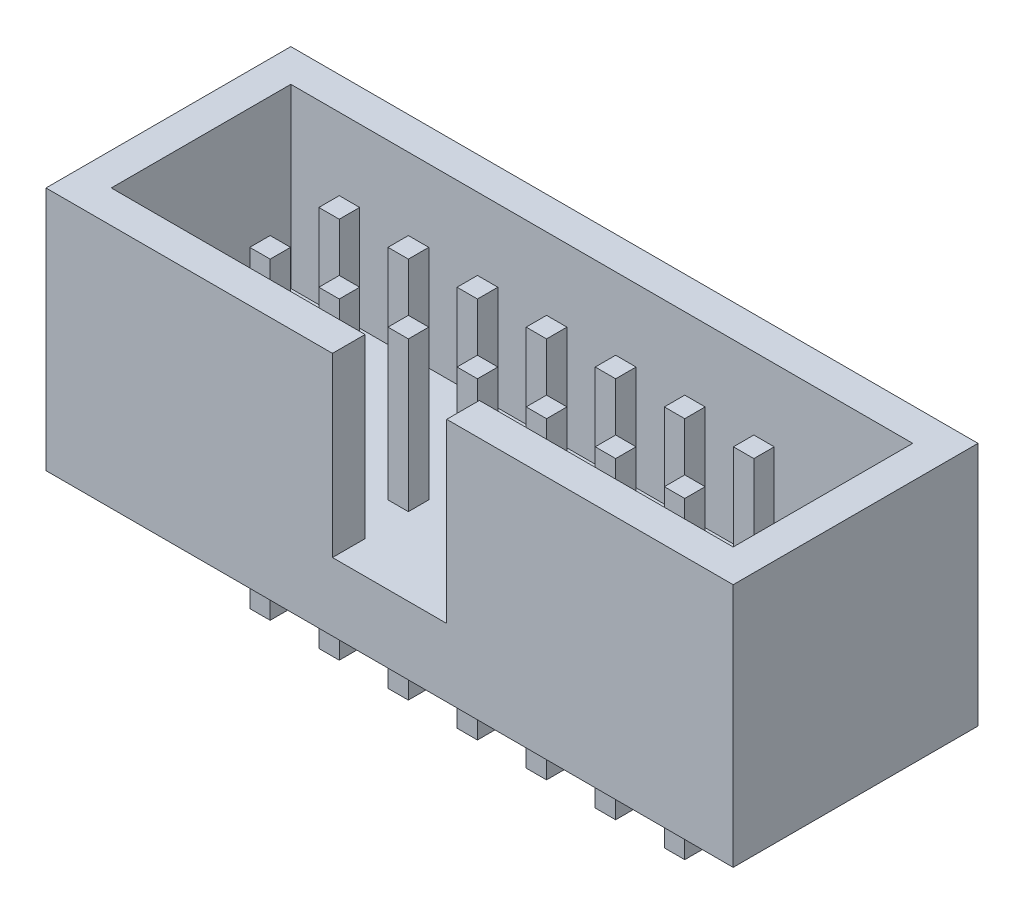
SolidWorks part; units mm, degrees
ref_plane "前视基准面" through (0, 0, 0) normal (0, 0, 1) x (1, 0, 0)
ref_plane "上视基准面" through (0, 0, 0) normal (0, 1, 0) x (1, 0, 0)
ref_plane "右视基准面" through (0, 0, 0) normal (1, 0, 0) x (0, 0, -1)
sketch "草图1" plane through (0, 0, 0) normal (0, 1, 0) x (1, 0, 0)
  line L0 (0, 85.0964) -> (0, -118.2031) construction
  line L1 (-12.63, 4.5) -> (12.63, 4.5)
  line L2 (-12.63, 4.5) -> (-12.63, -4.5)
  line L3 (-12.63, -4.5) -> (12.63, -4.5)
  line L4 (12.63, 4.5) -> (12.63, -4.5)
  line L5 (-200.5452, 0) -> (261.2352, 0) construction
  dimension "D1" = 9
  dimension "D2" = 25.26
extrude "拉伸1" add sketch "草图1" along normal blind 9
sketch "草图2" plane through (0, 9, 0) normal (0, 1, 0) x (-1, 0, 0)
  line L8 (-11.43, 3.3) -> (-11.43, -3.3)
  line L9 (11.43, 3.3) -> (-11.43, 3.3)
  line L10 (11.43, -3.3) -> (11.43, 3.3)
  line L11 (-11.43, -3.3) -> (11.43, -3.3)
  line L12 (-11.43, 3.3) -> (-11.43, -3.3)
  line L13 (11.43, 3.3) -> (-11.43, 3.3)
  line L14 (11.43, -3.3) -> (11.43, 3.3)
  line L15 (-11.43, -3.3) -> (11.43, -3.3)
  dimension "D1" = 1.2
extrude "切除-拉伸1" cut sketch "草图2" against normal blind 6.5
sketch "草图3" plane through (0, 0, 4.5) normal (0, 0, 1) x (1, 0, 0)
  line L0 (-12.63, 9) -> (12.63, 9) construction
  line L1 (-2.1, 9) -> (2.1, 9)
  line L2 (-2.1, 9) -> (-2.1, 2.5)
  line L3 (-2.1, 2.5) -> (2.1, 2.5)
  line L4 (2.1, 9) -> (2.1, 2.5)
  line L5 (-11.43, 2.5) -> (11.43, 2.5) construction
  line L6 (0, 9.4226) -> (0, -4.0288) construction
  dimension "D1" = 4.2
extrude "切除-拉伸2" cut sketch "草图3" against normal blind 6.5
sketch "草图5" plane through (0, 0, 0) normal (0, -1, 0) x (1, 0, 0)
  line L0 (0, 6.0683) -> (0, -6.9786) construction
  line L1 (-21.1981, 0) -> (21.4095, 0) construction
  line L2 (-2.4898, 1.27) -> (1.0953, 1.27) construction
  line L3 (-0.375, 0.895) -> (0.375, 0.895)
  line L4 (-0.375, 0.895) -> (-0.375, 1.645)
  line L5 (-0.375, 1.645) -> (0.375, 1.645)
  line L6 (0.375, 0.895) -> (0.375, 1.645)
  line L7 (2.165, 0.895) -> (2.915, 0.895)
  line L8 (2.165, 0.895) -> (2.165, 1.645)
  line L9 (2.165, 1.645) -> (2.915, 1.645)
  line L10 (2.915, 0.895) -> (2.915, 1.645)
  line L11 (4.705, 0.895) -> (5.455, 0.895)
  line L12 (4.705, 0.895) -> (4.705, 1.645)
  line L13 (4.705, 1.645) -> (5.455, 1.645)
  line L14 (5.455, 0.895) -> (5.455, 1.645)
  line L15 (7.245, 0.895) -> (7.995, 0.895)
  line L16 (7.245, 0.895) -> (7.245, 1.645)
  line L17 (7.245, 1.645) -> (7.995, 1.645)
  line L18 (7.995, 0.895) -> (7.995, 1.645)
  line L31 (-2.915, 0.895) -> (-2.165, 0.895)
  line L32 (-2.915, 0.895) -> (-2.915, 1.645)
  line L33 (-2.915, 1.645) -> (-2.165, 1.645)
  line L34 (-2.165, 0.895) -> (-2.165, 1.645)
  line L35 (-5.455, 0.895) -> (-4.705, 0.895)
  line L36 (-5.455, 0.895) -> (-5.455, 1.645)
  line L37 (-5.455, 1.645) -> (-4.705, 1.645)
  line L38 (-4.705, 0.895) -> (-4.705, 1.645)
  line L39 (-7.995, 0.895) -> (-7.245, 0.895)
  line L40 (-7.995, 0.895) -> (-7.995, 1.645)
  line L41 (-7.995, 1.645) -> (-7.245, 1.645)
  line L42 (-7.245, 0.895) -> (-7.245, 1.645)
  line L55 (-2.4898, -1.27) -> (1.0953, -1.27) construction
  line L68 (-7.245, -0.895) -> (-7.245, -1.645)
  line L69 (-7.995, -1.645) -> (-7.245, -1.645)
  line L70 (-7.995, -0.895) -> (-7.995, -1.645)
  line L71 (-7.995, -0.895) -> (-7.245, -0.895)
  line L72 (-4.705, -0.895) -> (-4.705, -1.645)
  line L73 (-5.455, -1.645) -> (-4.705, -1.645)
  line L74 (-5.455, -0.895) -> (-5.455, -1.645)
  line L75 (-5.455, -0.895) -> (-4.705, -0.895)
  line L76 (-2.165, -0.895) -> (-2.165, -1.645)
  line L77 (-2.915, -1.645) -> (-2.165, -1.645)
  line L78 (-2.915, -0.895) -> (-2.915, -1.645)
  line L79 (-2.915, -0.895) -> (-2.165, -0.895)
  line L92 (7.995, -0.895) -> (7.995, -1.645)
  line L93 (7.245, -1.645) -> (7.995, -1.645)
  line L94 (7.245, -0.895) -> (7.245, -1.645)
  line L95 (7.245, -0.895) -> (7.995, -0.895)
  line L96 (5.455, -0.895) -> (5.455, -1.645)
  line L97 (4.705, -1.645) -> (5.455, -1.645)
  line L98 (4.705, -0.895) -> (4.705, -1.645)
  line L99 (4.705, -0.895) -> (5.455, -0.895)
  line L100 (2.915, -0.895) -> (2.915, -1.645)
  line L101 (2.165, -1.645) -> (2.915, -1.645)
  line L102 (2.165, -0.895) -> (2.165, -1.645)
  line L103 (2.165, -0.895) -> (2.915, -0.895)
  line L104 (0.375, -0.895) -> (0.375, -1.645)
  line L105 (-0.375, -1.645) -> (0.375, -1.645)
  line L106 (-0.375, -0.895) -> (-0.375, -1.645)
  line L107 (-0.375, -0.895) -> (0.375, -0.895)
  dimension "D1" = 0.75
  dimension "D2" = 0.75
  dimension "D3" = 1.27
extrude "拉伸2" add sketch "草图5" along normal blind 3.5 and the other way offset from surface 1 other way up to face at (0, 9, 1.3)
